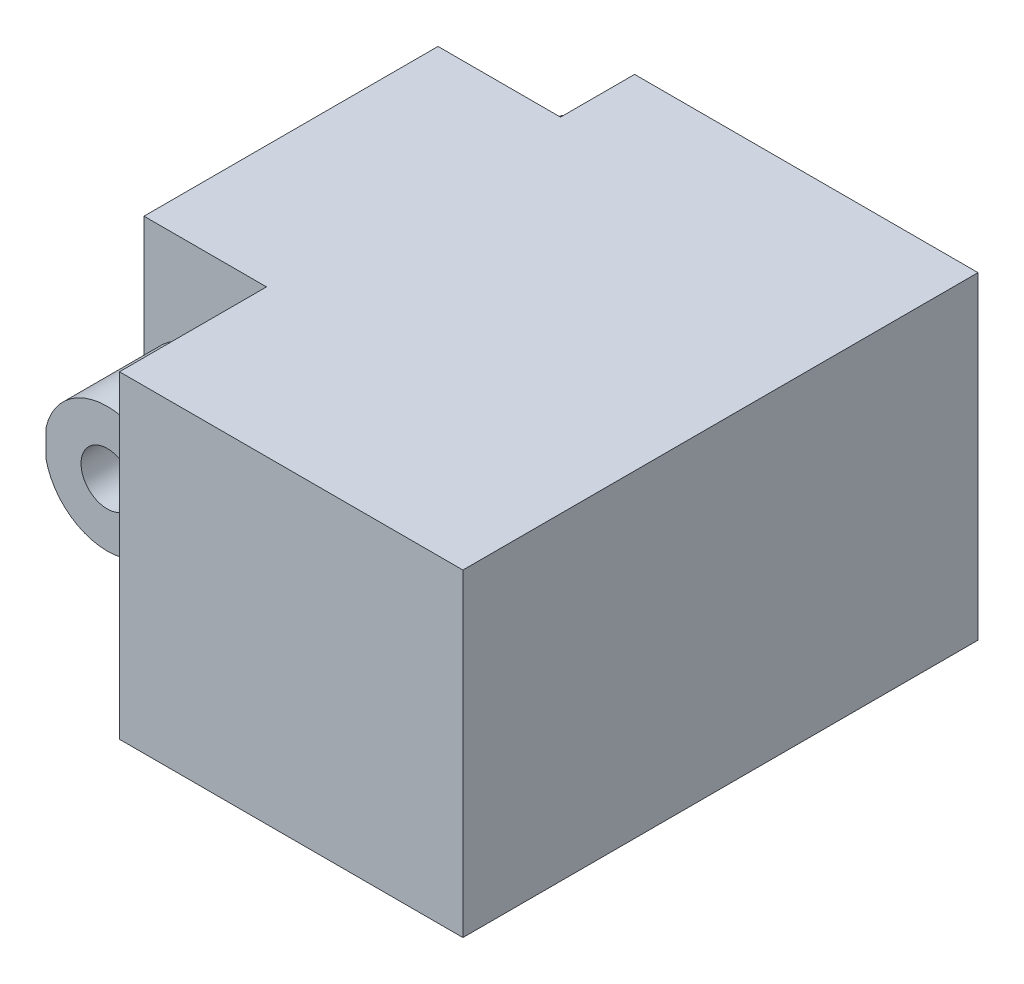
SolidWorks part; units mm, degrees
ref_plane "Płaszczyzna przednia" through (0, 0, 0) normal (0, 0, 1) x (1, 0, 0)
ref_plane "Płaszczyzna górna" through (0, 0, 0) normal (0, 1, 0) x (1, 0, 0)
ref_plane "Płaszczyzna prawa" through (0, 0, 0) normal (1, 0, 0) x (0, 0, -1)
sketch "Szkic1" plane through (0, 0, 0) normal (0, 0, 1) x (1, 0, 0)
  line L1 (0, 0) -> (356, 0)
  line L2 (0, 0) -> (0, 330)
  line L3 (0, 330) -> (356, 330)
  line L4 (356, 0) -> (356, 330)
  dimension "D1" = 330
  dimension "D2" = 356
extrude "Dodanie-wyciągnięcie1" add sketch "Szkic1" along normal blind 534
ref_plane "Płaszczyzna1" through (0, 0, 229.2) normal (0, 0, 1) x (1, 0, 0)
sketch "Szkic2" plane through (0, 0, 0) normal (-1, 0, 0) x (0, 0, 1)
  line L0 (534, 330) -> (229.2, 330) construction
  line L1 (534, 330) -> (0, 330) construction
  line L2 (229.2, 330) -> (229.2, 0) construction
  line L3 (534, 0) -> (0, 0) construction
  line L4 (229.2, 330) -> (381.6, 330)
  line L5 (229.2, 330) -> (76.8, 330)
  line L6 (381.6, 330) -> (229.2, 330)
  line L7 (381.6, 330) -> (381.6, 0)
  line L8 (381.6, 0) -> (229.2, 0)
  line L9 (229.2, 330) -> (229.2, 0)
  line L10 (76.8, 330) -> (76.8, 241.8495)
  line L11 (76.8, 330) -> (229.2, 330)
  line L12 (76.8, 330) -> (76.8, 0)
  line L13 (76.8, 0) -> (229.2, 0)
  line L14 (229.2, 330) -> (229.2, 0)
  line L15 (76.8, 241.8495) -> (76.8, 111.8495)
  line L16 (76.8, 111.8495) -> (-24.8, 111.8495)
  line L17 (-24.8, 111.8495) -> (-24.8, 241.8495)
  line L18 (-24.8, 241.8495) -> (76.8, 241.8495)
  line L19 (381.6, 241.8495) -> (483.2, 241.8495)
  line L21 (483.2, 241.8495) -> (381.6, 241.8495)
  line L22 (483.2, 241.8495) -> (483.2, 111.8495)
  line L23 (483.2, 111.8495) -> (381.6, 111.8495)
  line L24 (381.6, 241.8495) -> (381.6, 111.8495)
  line M1 (0, 330) -> (0, 0)
  line M2 (0, 0) -> (534, 0)
  line M4 (534, 330) -> (0, 330)
  dimension "D1" = 101.6
  dimension "D2" = 101.6
extrude "Dodanie-wyciągnięcie2" add sketch "Szkic2" along normal blind 127 contours L10 L12 L9 M2 M4 | L9 L7 M4 M2 | L18 L16 L12 M1 | L23 L22 L19 L7 | L18 L17 L16 M1 region at (0, 165, 153) region at (0, 165, 305.4) region at (0, 176.8495, 432.4) region at (0, 176.8495, 38.4) region at (0, 176.8495, -12.4)
sketch "Szkic3" plane through (0, 0, 483.2) normal (0, 0, 1) x (1, 0, 0)
  line L0 (-127, 241.8495) -> (0, 111.8495)
  line L1 (-127, 111.8495) -> (0, 241.8495)
  line L3 (-127, 241.8495) -> (0, 241.8495)
  line L4 (-127, 241.8495) -> (-127, 111.8495)
  line L5 (-127, 111.8495) -> (0, 111.8495)
  line L6 (0, 241.8495) -> (0, 111.8495)
  circle A0 centre (-63.5, 176.8495) radius 65
  circle A1 centre (-63.5, 176.8495) radius 27.2358
  line M1 (0, 111.8495) -> (0, 241.8495)
  line M2 (0, 241.8495) -> (-127, 241.8495)
  line M3 (-127, 241.8495) -> (-127, 111.8495)
  line M4 (-127, 111.8495) -> (0, 111.8495)
extrude "Wytnij-wyciągnięcie1" cut sketch "Szkic3" against normal up to surface (101.6 mm away) contours A0 L3 L0 | A0 L0 M3 | A0 L1 M2 | A0 L1 M1 | A0 L0 M1 | A0 L5 L0 | A0 L1 M4 | A0 L1 M3 region at (-104.5523, 236.1601, 483.2) region at (-121.33, 220.5592, 483.2) region at (-22.4477, 236.1601, 483.2) region at (-5.67, 220.5592, 483.2) region at (-121.33, 133.1397, 483.2) region at (-104.5523, 117.5388, 483.2) region at (-5.67, 133.1397, 483.2) region at (-22.4477, 117.5388, 483.2) up to face at (-63.5, 285.9247, 381.6)
sketch "Szkic5" plane through (0, 0, 483.2) normal (0, 0, 1) x (1, 0, 0)
  circle A0 centre (-63.5, 176.8495) radius 27.1878
extrude "Wytnij-wyciągnięcie2" cut sketch "Szkic5" against normal through all
sketch "Szkic6" plane through (0, 0, -24.8) normal (0, 0, -1) x (-1, 0, 0)
  line L1 (0, 241.8495) -> (127, 241.8495)
  line L2 (0, 241.8495) -> (0, 111.8495)
  line L3 (0, 111.8495) -> (127, 111.8495)
  line L4 (127, 241.8495) -> (127, 111.8495)
  circle A1 centre (63.5, 176.8495) radius 65
  line M2 (0, 241.8495) -> (0, 111.8495)
  line M3 (0, 111.8495) -> (127, 111.8495)
  line M4 (127, 111.8495) -> (127, 241.8495)
  line M5 (127, 241.8495) -> (0, 241.8495)
extrude "Wytnij-wyciągnięcie13" cut sketch "Szkic6" against normal up to surface (101.6 mm away) contours A1 L1 M2 | A1 M4 M5 | A1 L3 M4 | A1 M2 M3 region at (-14.4196, 228.6952, -24.8) region at (-112.5804, 228.6952, -24.8) region at (-14.4196, 125.0038, -24.8) region at (-112.5804, 125.0038, -24.8) up to face at (-63.5, 285.9247, 76.8)
